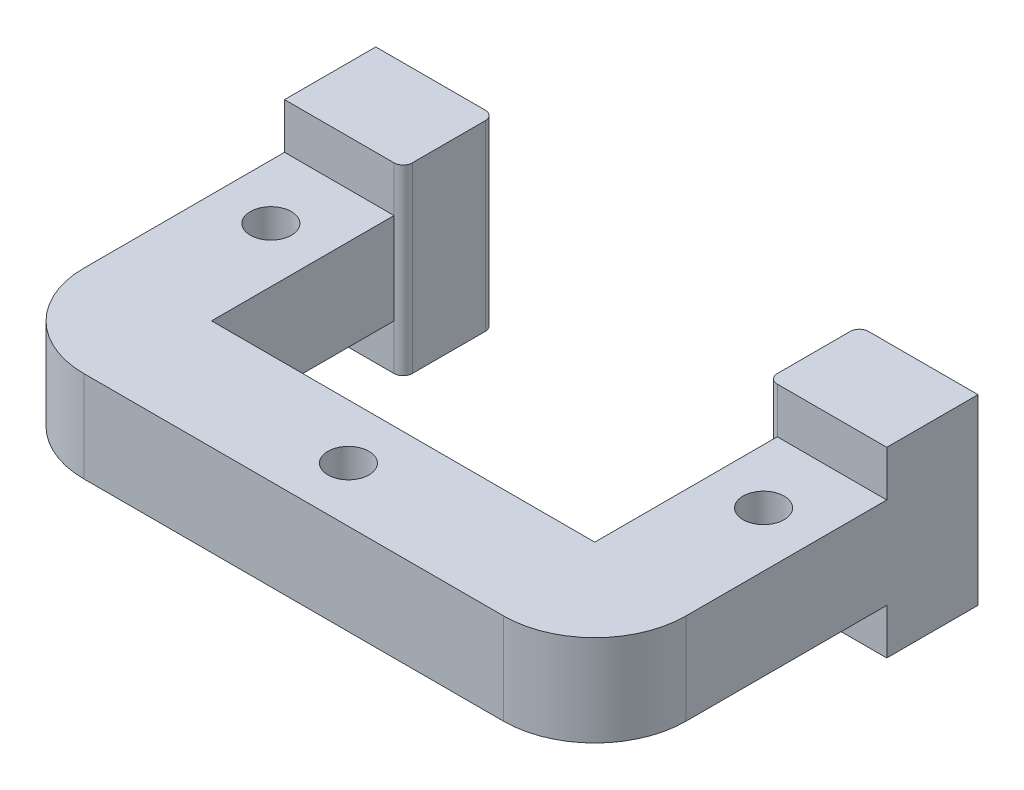
SolidWorks part; units mm, degrees
material "ABS"
ref_plane "Front Plane" through (0, 0, 0) normal (0, 0, 1) x (1, 0, 0)
ref_plane "Top Plane" through (0, 0, 0) normal (0, 1, 0) x (1, 0, 0)
ref_plane "Right Plane" through (0, 0, 0) normal (1, 0, 0) x (0, 0, -1)
sketch "Sketch1" plane through (0, 0, 0) normal (0, 1, 0) x (1, 0, 0)
  line L0 (0, 30.876) -> (0, -57.2152) construction
  line L1 (-20, 0) -> (-33, 0)
  line L2 (-33, 0) -> (-33, -42)
  line L3 (-33, -42) -> (33, -42)
  line L4 (33, -42) -> (33, 0)
  line L5 (33, 0) -> (20, 0)
  line L6 (20, 0) -> (20, -10)
  line L7 (21.5, -30) -> (-21.5, -30)
  line L8 (-20, -10) -> (-20, 0)
  line L9 (-20, -10) -> (-21, -10)
  line L10 (-21, -10) -> (-21, -30)
  line L11 (-21, -30) -> (-21.5, -30)
  line L12 (21, -30) -> (21.5, -30)
  line L13 (20, -10) -> (21, -10)
  line L14 (21, -10) -> (21, -30)
  point P5 (-26.5, 0)
  dimension "D1" = 40
  dimension "D2" = 13
  dimension "D3" = 30
  dimension "D4" = 12
  dimension "D5" = 10
  dimension "D6" = 1
extrude "Boss-Extrude1" add sketch "Sketch1" along normal blind 20 contours L0 L7 L10 L9 L8 L1 L2 L3 | L7 L0 L3 L4 L5 L6 L13 L14 region at (21.4869, 0, 25.7258) region at (-21.4869, 0, 25.7258)
sketch "Sketch2" plane through (0, 0, 0) normal (0, 0, -1) x (-1, 0, 0)
  line L3 (-33, 20) -> (-20, 20) construction
  line L4 (0, 0) -> (0, 42.0055) construction
  circle A2 centre (-24.25, 14.79) radius 2.75
  circle A3 centre (-24.25, 4.79) radius 2.75
  point P6 (-24.25, 14.79)
  point P9 (0, 0)
  point P11 (-24.25, 4.79)
  dimension "D4" = 5.5
  dimension "D1" = 5.21
  dimension "D2" = 24.25
  dimension "D3" = 15.21
extrude "Cut-Extrude1" cut sketch "Sketch2" against normal blind 8
mirror "Mirror1" about plane through (0, 0, 0) normal (1, 0, 0) of "Cut-Extrude1"
fillet "Fillet1" radius 1 4 edges at (-20, 10, 0) (20, 10, 0) (20, 10, 10) (-20, 10, 10)
sketch "Sketch7" plane through (0, 0, 0) normal (0, -1, 0) x (1, 0, 0)
  line L0 (21, 30) -> (-21, 30) construction
  line L1 (-21, 10) -> (-33, 10)
  line L2 (-21, 10) -> (-21, 30)
  line L3 (-21, 42) -> (-33, 42)
  line L4 (-33, 10) -> (-33, 42)
  line L5 (21, 10) -> (33, 10)
  line L6 (21, 10) -> (21, 30)
  line L7 (21, 42) -> (33, 42)
  line L8 (33, 10) -> (33, 42)
  line L9 (-21, 42) -> (21, 42)
  line L10 (-21, 42) -> (-21, 30)
  line L11 (-21, 30) -> (21, 30)
  line L15 (21, 42) -> (21, 30)
  line M57 (21, 30) -> (21, 10)
  line M62 (33, 0) -> (33, 42)
  line M63 (33, 42) -> (-33, 42)
extrude "Cut-Extrude3" cut sketch "Sketch7" against normal blind 5 contours L3 | L15 L5 M63 M57 M62 | L10 L9 L15 L11 region at (-27, 0, 26) region at (27, 0, 26)
ref_plane "Plane2" through (0, 10, 0) normal (0, 1, 0) x (1, 0, 0)
mirror "Mirror2" about plane through (0, 10, 0) normal (0, 1, 0) of "Cut-Extrude3"
sketch "Sketch9" plane through (0, 5, 0) normal (0, -1, 0) x (1, 0, 0)
  line L0 (-33, 36) -> (33, 36) construction
  line L1 (-27, 10) -> (-27, 42) construction
  line L2 (0, 51.8317) -> (0, -8.1141) construction
  line L3 (33, 10) -> (33, 42) construction
  line L4 (-33, 42) -> (-33, 10) construction
  line L5 (-21, 30) -> (-21, 10) construction
  line L8 (-33, 42) -> (-33, 10)
  line L9 (21, 30) -> (21, 10)
  line L10 (21, 30) -> (21, 10)
  line L11 (33, 42) -> (-33, 42)
  line L14 (-21, 10) -> (-21, 30)
  line L19 (33, 42) -> (-33, 42)
  line L24 (-33, 10) -> (-21, 10)
  line L25 (-33, 10) -> (-21, 10)
  line L29 (33, 10) -> (33, 42)
  line L30 (33, 10) -> (33, 42)
  line L31 (-21, 30) -> (21, 30)
  line L32 (-21, 30) -> (21, 30)
  line L33 (21, 10) -> (33, 10)
  line L34 (21, 10) -> (33, 10)
  circle A0 centre (0, 36) radius 2.25
  circle A1 centre (-27, 17.5) radius 2.25
  circle A2 centre (27, 17.5) radius 2.25
  point P0 (-33, 36)
  dimension "D2" = 4.5
  dimension "D1" = 0
extrude "Cut-Extrude5" cut sketch "Sketch9" against normal through all contours A1 | A2 | A0 region at (-27, 5, 17.5) region at (27, 5, 17.5)
fillet "Fillet3" radius 10 2 edges at (33, 10, 42) (-33, 10, 42)
